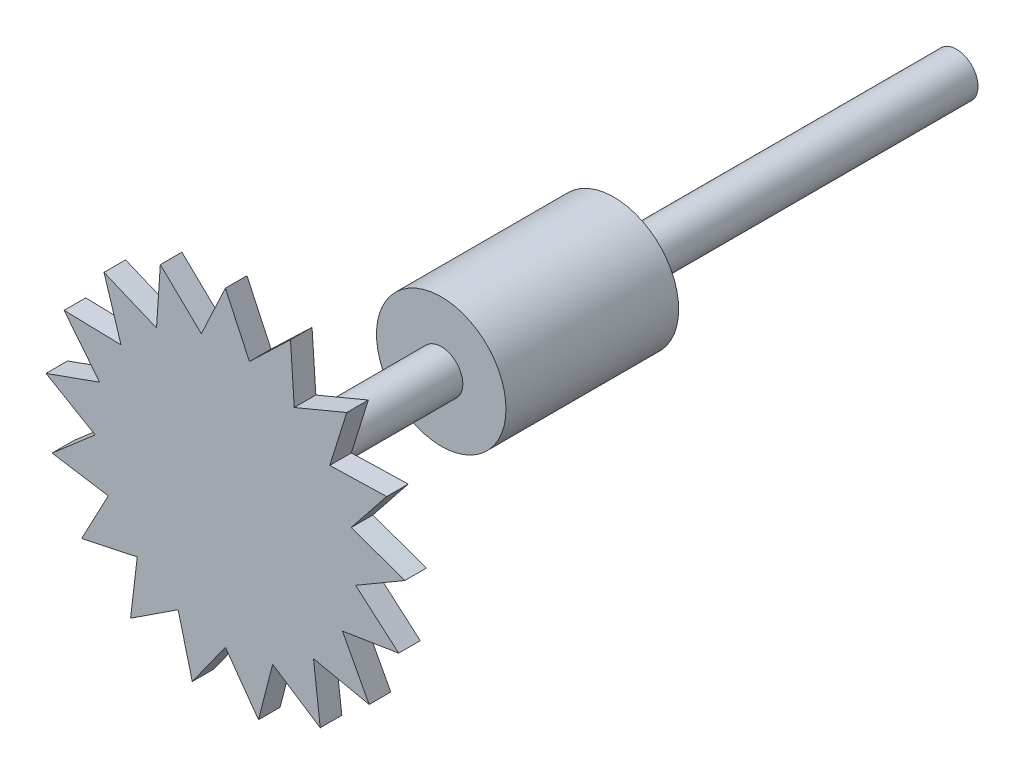
SolidWorks part; units mm, degrees
ref_plane "Plan de face" through (0, 0, 0) normal (0, 0, 1) x (1, 0, 0)
ref_plane "Plan de dessus" through (0, 0, 0) normal (0, 1, 0) x (1, 0, 0)
ref_plane "Plan de droite" through (0, 0, 0) normal (1, 0, 0) x (0, 0, -1)
sketch "Esquisse1" plane through (0, 0, 0) normal (0, 0, 1) x (1, 0, 0)
  circle A0 centre (0, 0) radius 15
extrude "Boss.-Extru.1" add sketch "Esquisse1" along normal blind 20 and the other way blind 20
sketch "Esquisse2" plane through (0, 0, 20) normal (0, 0, 1) x (1, 0, 0)
  circle A0 centre (0, 0) radius 5
extrude "Boss.-Extru.2" add sketch "Esquisse2" along normal blind 50
sketch "Esquisse3" plane through (0, 0, 70) normal (0, 0, 1) x (1, 0, 0)
  line L7 (-1.5716, 38.3615) -> (-5.5682, 29.7871)
  line L8 (1.5716, 38.3615) -> (5.5682, 29.7871)
  line L9 (-1.5716, 38.3615) -> (0, 41.7332)
  line L10 (0, 41.7332) -> (1.5716, 38.3615)
  line L11 (12.3923, 36.3387) -> (5.5682, 29.7871)
  line L12 (12.3923, 36.3387) -> (15.0758, 38.915)
  line L13 (15.0758, 38.915) -> (15.3232, 35.2033)
  line L14 (15.3232, 35.2033) -> (15.9525, 25.7642)
  line L15 (24.6826, 29.4082) -> (15.9525, 25.7642)
  line L16 (24.6826, 29.4082) -> (28.1155, 30.8412)
  line L17 (28.1155, 30.8412) -> (27.0054, 27.2907)
  line L18 (27.0054, 27.2907) -> (24.1823, 18.2617)
  line L19 (33.6393, 18.506) -> (24.1823, 18.2617)
  line L20 (33.6393, 18.506) -> (37.358, 18.6021)
  line L21 (37.358, 18.6021) -> (35.0403, 15.6924)
  line L22 (35.0403, 15.6924) -> (29.1462, 8.2928)
  line L23 (38.0528, 5.1044) -> (29.1462, 8.2928)
  line L24 (38.0528, 5.1044) -> (41.5552, 3.8507)
  line L25 (41.5552, 3.8507) -> (38.3428, 1.9747)
  line L26 (38.3428, 1.9747) -> (30.1738, -2.796)
  line L27 (37.3271, -8.9865) -> (30.1738, -2.796)
  line L28 (37.3271, -8.9865) -> (40.1401, -11.4208)
  line L29 (40.1401, -11.4208) -> (36.467, -12.0097)
  line L30 (36.467, -12.0097) -> (27.1262, -13.5072)
  line L31 (31.5602, -21.8638) -> (27.1262, -13.5072)
  line L32 (31.5602, -21.8638) -> (33.3038, -25.1499)
  line L33 (33.3038, -25.1499) -> (29.666, -24.3721)
  line L34 (29.666, -24.3721) -> (20.415, -22.3942)
  line L35 (21.5309, -31.7883) -> (20.415, -22.3942)
  line L36 (21.5309, -31.7883) -> (21.9697, -35.4823)
  line L37 (21.9697, -35.4823) -> (18.8585, -33.4429)
  line L38 (18.8585, -33.4429) -> (10.9467, -28.2567)
  line L39 (8.5937, -37.4195) -> (10.9467, -28.2567)
  line L40 (8.5937, -37.4195) -> (7.6685, -41.0226)
  line L41 (7.6685, -41.0226) -> (5.5041, -37.9971)
  line L42 (5.5041, -37.9971) -> (0, -30.303)
  line L43 (-5.5041, -37.9971) -> (0, -30.303)
  line L44 (-5.5041, -37.9971) -> (-7.6685, -41.0226)
  line L45 (-7.6685, -41.0226) -> (-8.5937, -37.4195)
  line L46 (-8.5937, -37.4195) -> (-10.9467, -28.2567)
  line L47 (-18.8585, -33.4429) -> (-10.9467, -28.2567)
  line L48 (-18.8585, -33.4429) -> (-21.9697, -35.4823)
  line L49 (-21.9697, -35.4823) -> (-21.5309, -31.7883)
  line L50 (-21.5309, -31.7883) -> (-20.415, -22.3942)
  line L51 (-29.666, -24.3721) -> (-20.415, -22.3942)
  line L52 (-29.666, -24.3721) -> (-33.3038, -25.1499)
  line L53 (-33.3038, -25.1499) -> (-31.5602, -21.8638)
  line L54 (-31.5602, -21.8638) -> (-27.1262, -13.5072)
  line L55 (-36.467, -12.0097) -> (-27.1262, -13.5072)
  line L56 (-36.467, -12.0097) -> (-40.1401, -11.4208)
  line L57 (-40.1401, -11.4208) -> (-37.3271, -8.9865)
  line L58 (-37.3271, -8.9865) -> (-30.1738, -2.796)
  line L59 (-38.3428, 1.9747) -> (-30.1738, -2.796)
  line L60 (-38.3428, 1.9747) -> (-41.5552, 3.8507)
  line L61 (-41.5552, 3.8507) -> (-38.0528, 5.1044)
  line L62 (-38.0528, 5.1044) -> (-29.1462, 8.2928)
  line L63 (-35.0403, 15.6924) -> (-29.1462, 8.2928)
  line L64 (-35.0403, 15.6924) -> (-37.358, 18.6021)
  line L65 (-37.358, 18.6021) -> (-33.6393, 18.506)
  line L66 (-33.6393, 18.506) -> (-24.1823, 18.2617)
  line L67 (-27.0054, 27.2907) -> (-24.1823, 18.2617)
  line L68 (-27.0054, 27.2907) -> (-28.1155, 30.8412)
  line L69 (-28.1155, 30.8412) -> (-24.6826, 29.4082)
  line L70 (-24.6826, 29.4082) -> (-15.9525, 25.7642)
  line L71 (-15.3232, 35.2033) -> (-15.9525, 25.7642)
  line L72 (-15.3232, 35.2033) -> (-15.0758, 38.915)
  line L73 (-15.0758, 38.915) -> (-12.3923, 36.3387)
  line L74 (-12.3923, 36.3387) -> (-5.5682, 29.7871)
  point P0 (0, 0)
  point P101 (0, 0)
  dimension "D3" = 17
extrude "Boss.-Extru.4" add sketch "Esquisse3" against normal blind 5
sketch "Esquisse5" plane through (0, 0, -20) normal (0, 0, -1) x (-1, 0, 0)
  circle A0 centre (0, 0) radius 5
extrude "Boss.-Extru.5" add sketch "Esquisse5" along normal blind 79.35
